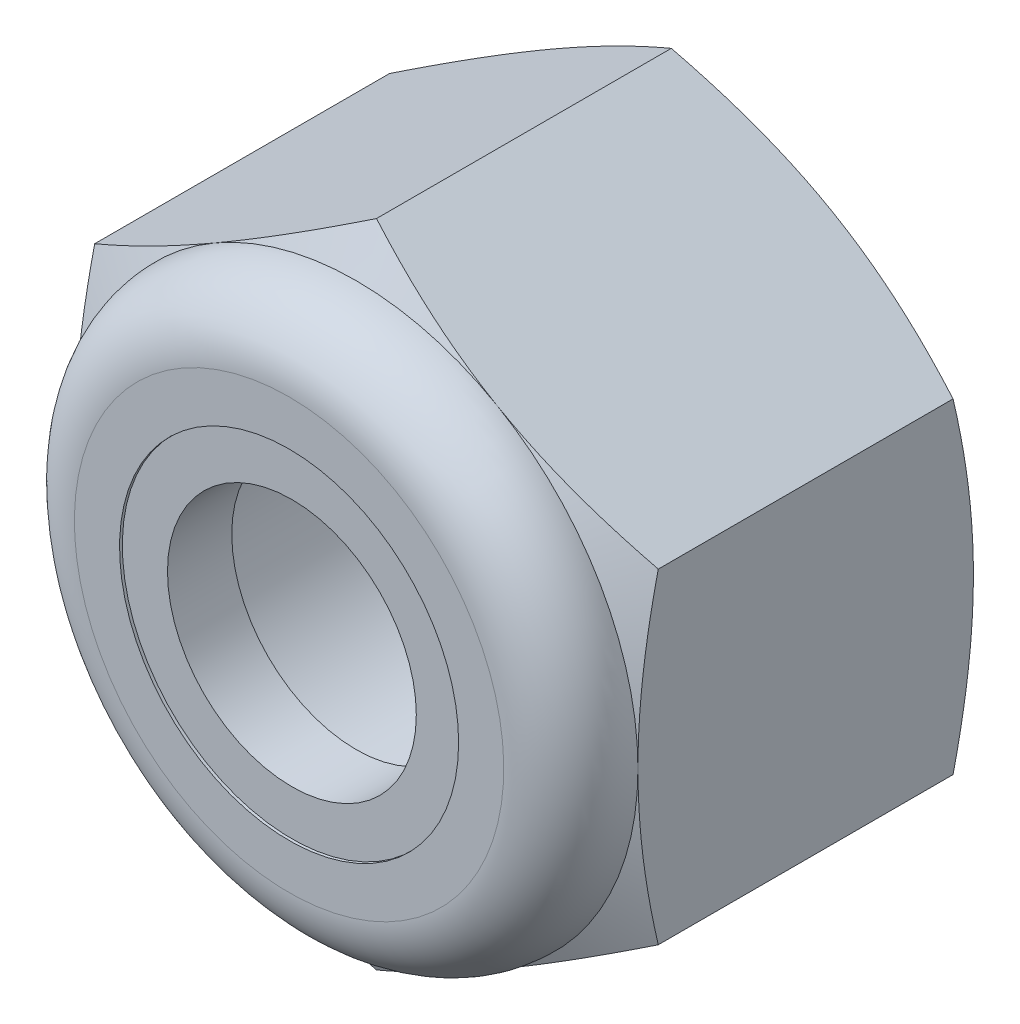
SolidWorks part; units mm, degrees
ref_plane "Front Plane" through (0, 0, 0) normal (0, 0, 1) x (1, 0, 0)
ref_plane "Top Plane" through (0, 0, 0) normal (0, 1, 0) x (1, 0, 0)
ref_plane "Right Plane" through (0, 0, 0) normal (1, 0, 0) x (0, 0, -1)
other "Configuration Table"
sketch "Sketch1" plane through (0, 0, 0) normal (0, 0, 1) x (1, 0, 0)
  line L1 (0, 4.0415) -> (-3.5, 2.0207)
  line L2 (-3.5, 2.0207) -> (-3.5, -2.0207)
  line L3 (-3.5, -2.0207) -> (0, -4.0415)
  line L4 (0, -4.0415) -> (3.5, -2.0207)
  line L5 (3.5, -2.0207) -> (3.5, 2.0207)
  line L6 (3.5, 2.0207) -> (0, 4.0415)
  circle A0 centre (0, 0) radius 3.5 construction
  circle A1 centre (0, 0) radius 2
  point P10 (0, -2)
  point P11 (0, 2)
  point P12 (0, 3.5)
  dimension "Thread Size" = 4
  dimension "Width" = 7
sketch "Sketch2" plane through (0, 0, 0) normal (1, 0, 0) x (0, 0, -1)
  line L0 (2.5, 0) -> (-2.5, 0) construction
  line L1 (-2.5, 2) -> (2.5, 2) construction
  line L2 (-2.465, -2.106) -> (-3.77, -2.106) construction
  line L3 (-3.1563, 2.0758) -> (-2.4563, 2.0758) construction
  line L4 (-2.4563, 2.0758) -> (-2.8063, 1.4696) construction
  line L5 (-2.8063, 1.4696) -> (-3.1563, 2.0758) construction
  line L6 (-3.1125, 2) -> (-2.5, 2) construction
  line L7 (-2.85, 1.5453) -> (-2.7625, 1.5453) construction
  line L8 (-2.8063, 1.5453) -> (-2.8063, 1.4696) construction
  line L9 (-2.8063, 2) -> (-2.8063, 2.0758) construction
  line L10 (-2.4781, 2.0379) -> (-3.1344, 2.0379)
  line L11 (-3.1344, 2.0379) -> (-2.85, 1.5453)
  line L12 (-2.85, 1.5453) -> (-2.7625, 1.5453)
  line L13 (-2.7625, 1.5453) -> (-2.4781, 2.0379)
  line L14 (2.5, 0) -> (3.77, 0)
  line L15 (3.77, 0) -> (3.77, 5.3115)
  line L16 (0, 5.3115) -> (0, 4.0415) construction
  line L17 (0, 4.0415) -> (0, 2.0207) construction
  line L18 (2.5, 3.5) -> (-1.6667, 3.5) construction
  line L19 (-2.85, -1.5453) -> (-2.7625, -1.5453) construction
  line L20 (2.5, 3.5) -> (2.5, 0)
  line L21 (2.2475, 4.0415) -> (-1.4142, 4.0415)
  line L22 (2.5, 3.5) -> (2.2475, 4.0415)
  line L23 (-2.5, 0) -> (-2.5, 2.6667) construction
  line L24 (-1.6667, 3.5) -> (-1.4142, 4.0415)
  line L25 (3.77, 5.3115) -> (-3.77, 5.3115)
  line L26 (-2.5, 2.6667) -> (-3.77, 2.6667)
  line L27 (-3.77, 2.6667) -> (-3.77, 5.3115)
  line L28 (-2.465, 2.6667) -> (-2.465, 1.5453) construction
  line L29 (-2.465, 2.106) -> (-3.77, 2.106)
  line L30 (-3.77, 2.106) -> (-3.77, 0)
  line L31 (-3.77, 0) -> (-1.6667, 0)
  line L32 (-1.6667, 0) -> (-1.6667, 3.465)
  line L33 (-2.465, 2.106) -> (-2.465, 2.6667)
  arc A0 (-1.6667, 3.5) -> (-2.5, 2.6667) centre (-1.6667, 2.6667) ccw
  arc A1 (-1.6667, 3.465) -> (-2.465, 2.6667) centre (-1.6667, 2.6667) ccw
  point P4 (0, 0)
  point P18 (-2.8063, 2.0379)
  point P22 (-2.8063, 2.0379)
  point P33 (0, 4.0415)
  point P48 (-3.77, -2.106)
  point P51 (-2.85, -1.5453)
  dimension "D2" = 1.27
  dimension "D3" = 25
  dimension "D5" = 25
sketch "Sketch3" plane through (0, 0, 0) normal (0, 0, 1) x (1, 0, 0)
  line L0 (0, -4.0415) -> (3.5, -2.0207) construction
  line L1 (3.5, -2.0207) -> (3.5, 2.0207) construction
  line L2 (3.5, 2.0207) -> (0, 4.0415) construction
  line L3 (0, 4.0415) -> (-3.5, 2.0207) construction
  line L4 (-3.5, 2.0207) -> (-3.5, -2.0207) construction
  line L5 (-3.5, -2.0207) -> (0, -4.0415) construction
  line L6 (0, -4.0415) -> (3.5, -2.0207)
  line L7 (3.5, -2.0207) -> (3.5, 2.0207)
  line L8 (3.5, 2.0207) -> (0, 4.0415)
  line L9 (0, 4.0415) -> (-3.5, 2.0207)
  line L10 (-3.5, 2.0207) -> (-3.5, -2.0207)
  line L11 (-3.5, -2.0207) -> (0, -4.0415)
  circle A0 centre (0, 0) radius 2 construction
  circle A1 centre (0, 0) radius 2
extrude "Boss-Extrude1" add sketch "Sketch3" along normal mid plane 5
sketch "Sketch4" plane through (0, 0, 0) normal (1, 0, 0) x (0, 0, -1)
  line L0 (3.77, 5.3115) -> (-3.77, 5.3115) construction
  line L1 (-3.77, 2.6667) -> (-3.77, 5.3115) construction
  line L2 (-2.5, 2.6667) -> (-3.77, 2.6667) construction
  line L3 (-1.6667, 3.5) -> (-1.4142, 4.0415) construction
  line L4 (2.2475, 4.0415) -> (-1.4142, 4.0415) construction
  line L5 (2.5, 3.5) -> (2.2475, 4.0415) construction
  line L6 (2.5, 3.5) -> (2.5, 0) construction
  line L7 (2.5, 0) -> (3.77, 0) construction
  line L8 (3.77, 0) -> (3.77, 5.3115) construction
  line L9 (-3.77, 2.106) -> (-3.77, 0) construction
  line L10 (-3.77, 0) -> (-1.6667, 0) construction
  line L11 (-1.6667, 0) -> (-1.6667, 3.465) construction
  line L12 (-2.465, 2.106) -> (-2.465, 2.6667) construction
  line L13 (-2.465, 2.106) -> (-3.77, 2.106) construction
  line L14 (3.77, 5.3115) -> (-3.77, 5.3115)
  line L15 (-3.77, 2.6667) -> (-3.77, 5.3115)
  line L16 (-2.5, 2.6667) -> (-3.77, 2.6667)
  line L17 (-1.6667, 3.5) -> (-1.4142, 4.0415)
  line L18 (2.2475, 4.0415) -> (-1.4142, 4.0415)
  line L19 (2.5, 3.5) -> (2.2475, 4.0415)
  line L20 (2.5, 3.5) -> (2.5, 0)
  line L21 (2.5, 0) -> (3.77, 0)
  line L22 (3.77, 0) -> (3.77, 5.3115)
  line L23 (-3.77, 2.106) -> (-3.77, 0)
  line L24 (-3.77, 0) -> (-1.6667, 0)
  line L25 (-1.6667, 0) -> (-1.6667, 3.465)
  line L26 (-2.465, 2.106) -> (-2.465, 2.6667)
  line L27 (-2.465, 2.106) -> (-3.77, 2.106)
  arc A0 (-1.6667, 3.5) -> (-2.5, 2.6667) centre (-1.6667, 2.6667) ccw construction
  arc A1 (-1.6667, 3.465) -> (-2.465, 2.6667) centre (-1.6667, 2.6667) ccw construction
  arc A2 (-1.6667, 3.5) -> (-2.5, 2.6667) centre (-1.6667, 2.6667) ccw
  arc A3 (-1.6667, 3.465) -> (-2.465, 2.6667) centre (-1.6667, 2.6667) ccw
revolve "Cut-Revolve1" cut sketch "Sketch4" angle 360 about L0
sketch "Sketch5" plane through (0, 0, 0) normal (1, 0, 0) x (0, 0, -1)
  line L0 (-2.465, 2.6667) -> (-2.465, 1.5453) construction
  line L1 (-1.6667, 0) -> (-1.6667, 3.465) construction
  line L2 (-2.465, 2.6667) -> (-2.465, 1.5453)
  line L3 (-1.6667, 1.5453) -> (-1.6667, 3.465)
  line L4 (-2.465, 1.5453) -> (-1.6667, 1.5453)
  arc A0 (-1.6667, 3.465) -> (-2.465, 2.6667) centre (-1.6667, 2.6667) ccw construction
  arc A1 (-1.6667, 3.465) -> (-2.465, 2.6667) centre (-1.6667, 2.6667) ccw
revolve "Revolve1" add sketch "Sketch5" angle 360 about L0
sketch "Sketch6" [suppressed] plane through (0, 0, 2.5) normal (0, 0, 1) x (1, 0, 0)
  circle A0 centre (0, 0) radius 2 construction
  circle A1 centre (0, 0) radius 2
curve "Helix/Spiral1" [suppressed] pitch 0.7 height 5.7 turns 8.1429
sketch "Sketch7" [suppressed] plane through (0, 0, 0) normal (1, 0, 0) x (0, 0, -1)
  line L0 (-3.1344, 2.0379) -> (-2.85, 1.5453) construction
  line L1 (-2.85, 1.5453) -> (-2.7625, 1.5453) construction
  line L2 (-2.7625, 1.5453) -> (-2.4781, 2.0379) construction
  line L3 (-2.4781, 2.0379) -> (-3.1344, 2.0379) construction
  line L4 (-3.1344, 2.0379) -> (-2.85, 1.5453)
  line L5 (-2.85, 1.5453) -> (-2.7625, 1.5453)
  line L6 (-2.7625, 1.5453) -> (-2.4781, 2.0379)
  line L7 (-2.4781, 2.0379) -> (-3.1344, 2.0379)
sweep "Sweep1" [suppressed] add profiles "Sketch7" path "Helix/Spiral1"
sketch "Sketch8" [suppressed] plane through (0, 0, -2.5) normal (0, 0, -1) x (-1, 0, 0)
  circle A2 centre (0, 0) radius 2.0379
  point P2 (0, 2.0379)
extrude "Cut-Extrude1" [suppressed] cut sketch "Sketch8" along normal through all and the other way through all draft 60
sketch "Sketch9" [suppressed] plane through (0, 0, 1.6667) normal (0, 0, 1) x (1, 0, 0)
  circle A2 centre (0, 0) radius 2.0379
  circle A3 centre (0, 0) radius 1.5453 construction
  point P2 (0, 2.0379)
  point P4 (0, 1.5453)
extrude "Cut-Extrude2" [suppressed] cut sketch "Sketch9" along normal through all and the other way through all draft 60
equation "\"D1@Sketch2\" = \"Pitch@Sketch2\" / 8"
equation "\"D4@Sketch2\"=\"Height@Sketch2\"/6"
equation "\"D1@Boss-Extrude1\"=\"Height@Sketch2\""
equation "\"D3@Helix/Spiral1\"=\"Height@Sketch2\"+\"Pitch@Sketch2\""
equation "\"D4@Helix/Spiral1\"=\"Pitch@Sketch2\""
equation "\"D6@Sketch2\"=\"Pitch@Sketch2\"*0.05"
